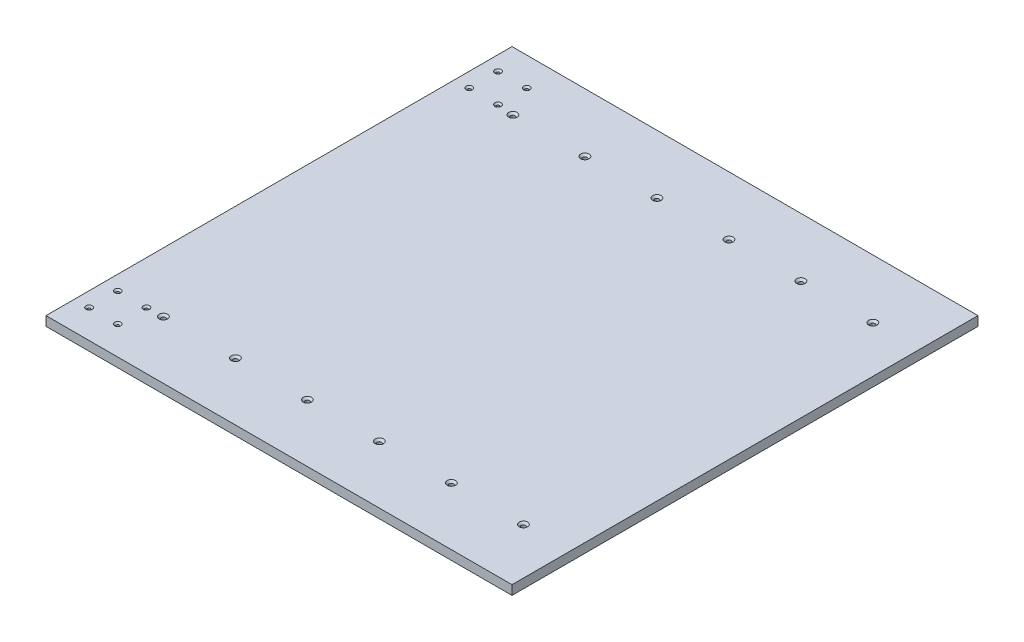
SolidWorks part; units mm, degrees
material "Buk"
ref_plane "Płaszczyzna przednia" through (0, 0, 0) normal (0, 0, 1) x (1, 0, 0)
ref_plane "Płaszczyzna górna" through (0, 0, 0) normal (0, 1, 0) x (1, 0, 0)
ref_plane "Płaszczyzna prawa" through (0, 0, 0) normal (1, 0, 0) x (0, 0, -1)
sketch "Szkic1" plane through (0, 0, 0) normal (0, 1, 0) x (1, 0, 0)
  line L1 (0, 0) -> (500, 0)
  line L2 (0, 0) -> (0, 500)
  line L3 (0, 500) -> (500, 500)
  line L4 (500, 0) -> (500, 500)
  dimension "D1" = 500
extrude "Dodanie-wyciągnięcie1" add sketch "Szkic1" along normal blind 10
sketch "Szkic2" plane through (0, 10, 0) normal (0, 1, 0) x (1, 0, 0)
  line L0 (0, 0) -> (500, 0) construction
  line L1 (0, 500) -> (0, 0) construction
  line L2 (0, 250) -> (500, 250) construction
  line L3 (500, 0) -> (500, 500) construction
  circle A0 centre (15.6, 30.6) radius 1.6
  circle A1 centre (15.6, 61.4) radius 1.6
  circle A2 centre (46.4, 61.4) radius 1.6
  circle A3 centre (46.4, 30.6) radius 1.6
  circle A4 centre (15.6, 438.6) radius 1.6
  circle A5 centre (15.6, 469.4) radius 1.6
  circle A6 centre (46.4, 469.4) radius 1.6
  circle A7 centre (46.4, 438.6) radius 1.6
  dimension "D1" = 3.2
  dimension "D2" = 3.2
  dimension "D3" = 3.2
  dimension "D4" = 3.2
  dimension "D5" = 30.6
  dimension "D6" = 30.6
  dimension "D7" = 30.8
  dimension "D8" = 15.6
  dimension "D9" = 15.6
  dimension "D10" = 30.8
  dimension "D11" = 30.8
  dimension "D12" = 30.8
hole_wizard "Pogłębienie stożkowe pod M3 Wkręt ustalający1" positions "Szkic3" profile "Szkic5" countersink size "M3" standard "Ansi Metric"
sketch "Szkic3" plane through (0, 10, 0) normal (0, 1, 0) x (1, 0, 0)
  point P0 (46.4, 30.6)
  point P3 (46.4, 61.4)
  point P6 (15.6, 61.4)
  point P9 (15.6, 30.6)
  point P12 (46.4, 438.6)
  point P15 (46.4, 469.4)
  point P18 (15.6, 469.4)
  point P21 (15.6, 438.6)
sketch "Szkic5" plane through (46.4, 10, -30.6) normal (1, 0, 0) x (0, 0, 1)
  line L0 (0, 0) -> (0, 11.0215)
  line L1 (0, 11.0215) -> (1.7, 10)
  line L2 (1.7, 10) -> (1.7, 1.66)
  line L3 (1.7, 1.66) -> (3.36, 0)
  line L5 (3.36, 0) -> (0, 0)
  line L6 (-1.7, 1.66) -> (-3.36, 0) construction
  line L10 (0, 11.0215) -> (-1.7, 10) construction
  line L11 (0, -6.35) -> (0, 107.95) construction
  dimension "Œrednica otworu" = 3.4
  dimension "G³êbokoœc otworu" = 10
  dimension "Œrednica zewnêtrznego pog³êbienia sto¿kowego" = 6.72
  dimension "K¹t zewnêtrznego pog³êbienia sto¿kowego" = 90
  dimension "K¹t wiert³a" = 118
hole_wizard "Pogłębienie stożkowe pod M4 Wkręt ustalający1" positions "Szkic6" profile "Szkic7" countersink size "M4" standard "Ansi Metric"
sketch "Szkic6" plane through (0, 10, 0) normal (0, 1, 0) x (1, 0, 0)
  line L0 (0, 500) -> (0, 0) construction
  line L1 (0, 0) -> (500, 0) construction
  point P0 (63.9, 62.07)
  point P14 (141.15, 62.07)
  point P15 (218.4, 62.07)
  point P16 (295.65, 62.07)
  point P17 (372.9, 62.07)
  point P18 (450.15, 62.07)
  point P19 (141.15, 437.07)
  point P20 (218.4, 437.07)
  point P21 (295.65, 437.07)
  point P22 (372.9, 437.07)
  point P23 (450.15, 437.07)
  point P24 (63.9, 437.07)
  dimension "D1" = 63.9
  dimension "D2" = 62.07
  dimension "D3" = 6
  dimension "D4" = 2
sketch "Szkic7" plane through (63.9, 10, -62.07) normal (1, 0, 0) x (0, 0, 1)
  line L0 (0, 0) -> (0, 12.9421)
  line L1 (0, 12.9421) -> (2.4, 11.5)
  line L2 (2.4, 11.5) -> (2.4, 2.08)
  line L3 (2.4, 2.08) -> (4.48, 0)
  line L5 (4.48, 0) -> (0, 0)
  line L6 (-2.4, 2.08) -> (-4.48, 0) construction
  line L10 (0, 12.9421) -> (-2.4, 11.5) construction
  line L11 (0, -6.35) -> (0, 107.95) construction
  dimension "Œrednica otworu" = 4.8
  dimension "G³êbokoœc otworu" = 11.5
  dimension "Œrednica zewnêtrznego pog³êbienia sto¿kowego" = 8.96
  dimension "K¹t zewnêtrznego pog³êbienia sto¿kowego" = 90
  dimension "K¹t wiert³a" = 118
